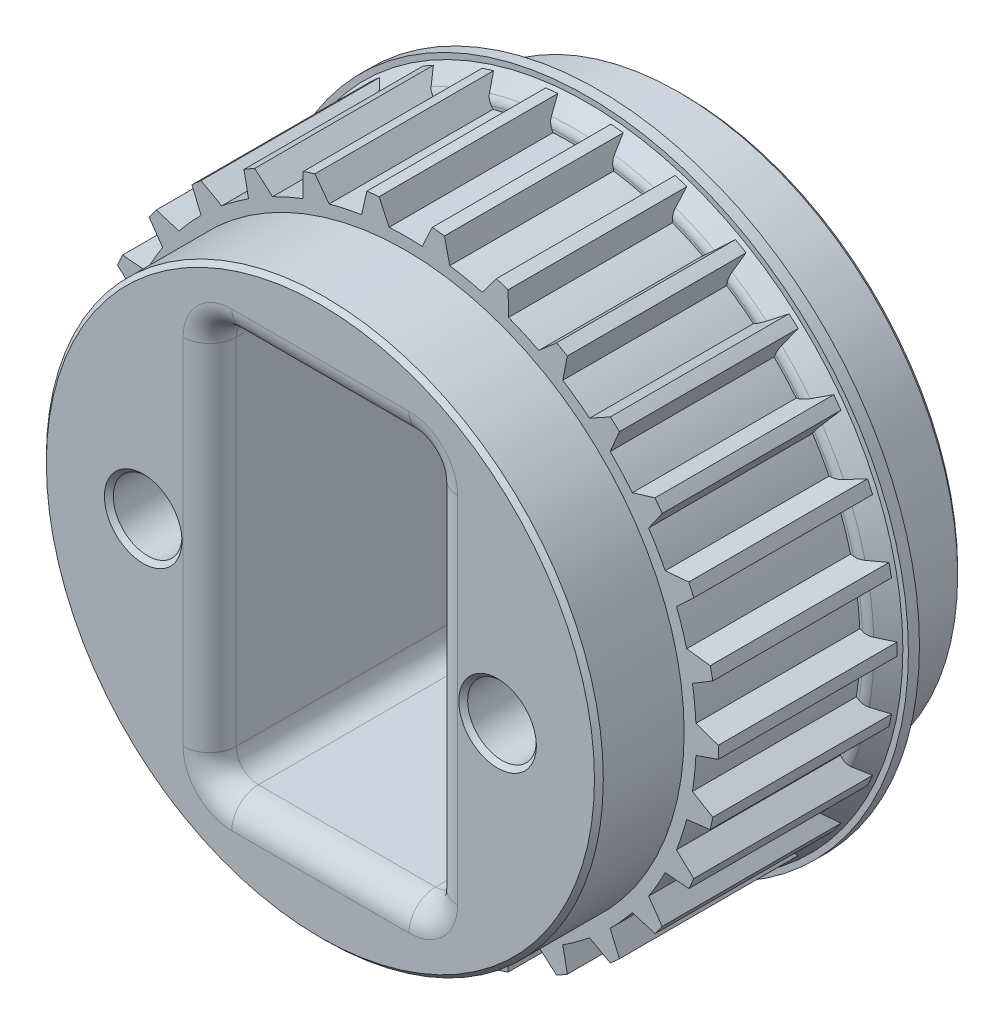
SolidWorks part; units mm, degrees
material "PMMA"
ref_plane "Ebene vorne" through (0, 0, 0) normal (0, 0, 1) x (1, 0, 0)
ref_plane "Ebene oben" through (0, 0, 0) normal (0, 1, 0) x (1, 0, 0)
ref_plane "Ebene rechts" through (0, 0, 0) normal (1, 0, 0) x (0, 0, -1)
ref_axis "Achse1" through (0, 0, 9.02) along (0, 0, -1)
sketch "Skizze1" plane through (0, 0, 0) normal (1, 0, 0) x (0, 0, -1)
  line L0 (0, 47.6717) -> (0, -53.1541) construction
  line L1 (-46.5152, 0) -> (56.3665, 0) construction
  line L2 (-4.35, 14.12) -> (4.35, 14.12)
  line L3 (4.35, 14.12) -> (4.35, 12.575)
  line L4 (4.35, 12.575) -> (8.2, 12.575)
  line L5 (8.2, 12.575) -> (8.2, 0)
  line L6 (8.2, 0) -> (-8.2, 0)
  line L7 (-8.2, 12.575) -> (-8.2, 0)
  line L8 (-4.35, 12.575) -> (-8.2, 12.575)
  line L9 (-4.35, 14.12) -> (-4.35, 12.575)
  point P12 (0, 0)
  point P15 (0, 14.12)
  dimension "D1" = 8.2
  dimension "D2" = 25.15
  dimension "D3" = 28.24
  dimension "D4" = 8.7
revolve "Rotation1" add sketch "Skizze1" angle 360 about L1
sketch "Skizze2" plane through (0, 0, 0) normal (0, 0, 1) x (1, 0, 0)
  line L0 (0, 30.4501) -> (0, -26.4561) construction
  line L1 (-21.1101, 0) -> (22.7837, 0) construction
  line L2 (-1.2, 14.0689) -> (-0.7476, 13.0987)
  line L3 (1.2, 14.0689) -> (0.7476, 13.0987)
  circle A0 centre (0, 0) radius 13.12 construction
  circle A1 centre (0, 0) radius 14.12 construction
  circle A2 centre (0, 0) radius 14.12 construction
  arc A3 (-1.2, 14.0689) -> (1.2, 14.0689) centre (0, 0) cw
  arc A4 (-0.7476, 13.0987) -> (0.7476, 13.0987) centre (0, 0) cw
  dimension "D1" = 28.24
  dimension "D2" = 26.24
  dimension "D6" = 1
  dimension "D3" = 50
  dimension "D4" = 2.4
  dimension "D5" = 1.4951
extrude "Schnitt-Linear austragen1" cut sketch "Skizze2" against normal through all and the other way through all
pattern_circular "Kreismuster1" count 30 over 360 about axis through (0, 0, 9.02) along (0, 0, -1) of "Schnitt-Linear austragen1"
sketch "Skizze3" plane through (0, 0, 0) normal (1, 0, 0) x (0, 0, -1)
  line L0 (4.35, 13) -> (4.35, 14.5)
  line L1 (4.35, 14.5) -> (3.85, 14.5)
  line L2 (3.85, 14.5) -> (3.85, 14.25)
  line L3 (3.85, 14.25) -> (3.1964, 13.5964)
  line L4 (3.05, 13.2429) -> (3.05, 13)
  line L5 (3.05, 13) -> (4.35, 13)
  line L6 (4.35, 13.0987) -> (4.35, 14.0689) construction
  line L7 (0, 19.3181) -> (0, -13.1661) construction
  line L8 (11.0313, 0) -> (-11.7934, 0) construction
  arc A0 (3.05, 13.2429) -> (3.1964, 13.5964) centre (3.55, 13.2429) cw
  dimension "D7" = 0.5
  dimension "D1" = 14.5
  dimension "D2" = 13
  dimension "D3" = 0.5
  dimension "D4" = 14.25
  dimension "D5" = 45
  dimension "D6" = 0.8
revolve "Rotation2" add sketch "Skizze3" angle 360 about L8
sketch "Skizze4" plane through (0, 0, 0) normal (0, 0, 1) x (1, 0, 0)
  line L0 (0, 24.4145) -> (0, -17.917) construction
  line L1 (-17.7015, 0) -> (18.3014, 0) construction
  line L2 (4, 9) -> (-4, 9)
  line L3 (-5, 8) -> (-5, -8)
  line L4 (5, 8) -> (5, -8)
  line L5 (4, -9) -> (-4, -9)
  arc A0 (-5, 8) -> (-4, 9) centre (-4, 8) cw
  arc A1 (5, 8) -> (4, 9) centre (4, 8) ccw
  arc A2 (5, -8) -> (4, -9) centre (4, -8) cw
  arc A3 (-5, -8) -> (-4, -9) centre (-4, -8) ccw
  circle A4 centre (-8, 0) radius 1.55
  circle A5 centre (8, 0) radius 1.55
  point P13 (-5, 0)
  point P14 (0, 9)
  point P20 (0, -9)
  point P21 (5, 0)
  dimension "D1" = 1
  dimension "D4" = 3.1
  dimension "D2" = 18
  dimension "D3" = 10
  dimension "D5" = 16
extrude "Schnitt-Linear austragen2" cut sketch "Skizze4" against normal through all and the other way through all
fillet "Verrundung1" radius 1.2 16 edges at (-4.7071, 8.7071, -8.2) (0, 9, -8.2) (4.7071, 8.7071, -8.2) (5, 0, -8.2) (4.7071, -8.7071, -8.2) (0, -9, -8.2) (-4.7071, -8.7071, -8.2) (-4.7071, 8.7071, 8.2) (0, 9, 8.2) (4.7071, 8.7071, 8.2) (5, 0, 8.2) (4.7071, -8.7071, 8.2) (0, -9, 8.2) (-4.7071, -8.7071, 8.2) (-5, 0, -8.2) (-5, 0, 8.2)
chamfer "Fase1" distance 0.2 angle 45 6 edges at (-6.45, 0, -8.2) (6.45, 0, -8.2) (6.45, 0, 8.2) (-6.45, 0, 8.2) (12.575, 0, -8.2) (12.575, 0, 8.2)
